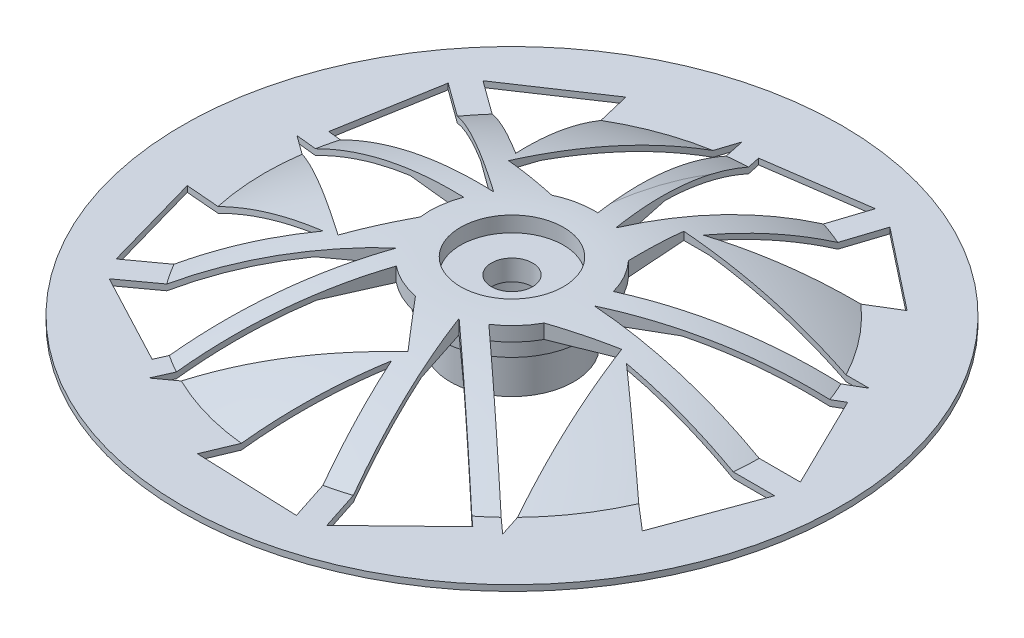
SolidWorks part; units mm, degrees
ref_plane "Front Plane" through (0, 0, 0) normal (0, 0, 1) x (1, 0, 0)
ref_plane "Top Plane" through (0, 0, 0) normal (0, 1, 0) x (1, 0, 0)
ref_plane "Right Plane" through (0, 0, 0) normal (1, 0, 0) x (0, 0, -1)
sketch "Sketch1" plane through (0, 0, 0) normal (0, 0, 1) x (1, 0, 0)
  line L0 (0, 0) -> (19.05, 0) construction
  line L1 (19.05, 0) -> (19.05, 12.7) construction
  line L2 (19.05, 12.7) -> (22.225, 12.7) construction
  line L3 (22.225, 12.7) -> (22.225, 19.05) construction
  line L4 (22.225, 19.05) -> (76.2, 19.05) construction
  line L5 (76.2, 19.05) -> (76.2, 6.35) construction
  line L6 (0, 0) -> (0, 22.225) construction
  line L7 (15.875, 0) -> (15.875, 22.225) construction
  line L8 (15.875, 22.225) -> (84.6295, 22.225) construction
  line L9 (15.875, 23.8125) -> (15.875, 19.05)
  line L10 (15.875, 0) -> (19.05, 0)
  line L11 (19.05, 0) -> (19.05, 12.7)
  line L12 (19.05, 12.7) -> (22.225, 12.7)
  line L13 (22.225, 12.7) -> (22.225, 19.05)
  line L14 (22.225, 19.05) -> (43.5904, 19.05)
  line L16 (76.2, 8.17) -> (101.6, 8.17) construction
  line L17 (101.6, 8.17) -> (101.6, 6.35) construction
  line L18 (101.6, 6.35) -> (76.2, 6.35) construction
  line L19 (76.2, 8.17) -> (101.6, 8.17)
  line L20 (101.6, 8.17) -> (101.6, 6.35)
  line L21 (101.6, 6.35) -> (76.2, 6.35)
  line L22 (6.35, 19.05) -> (15.875, 19.05)
  line L24 (0, 12.7) -> (0, 19.05) construction
  line L26 (6.35, 12.7) -> (6.35, 19.05) construction
  line L27 (6.35, 12.7) -> (15.875, 12.7)
  line L28 (6.35, 19.05) -> (6.35, 12.7)
  line L29 (15.875, 12.7) -> (15.875, 0)
  arc A0 (43.5904, 19.05) -> (76.2, 6.35) centre (15.875, -100.33) cw
  arc A1 (15.875, 23.8125) -> (76.2, 8.17) centre (15.875, -100.33) cw
  arc A3 (15.875, 22.225) -> (76.2, 6.35) centre (15.875, -100.33) cw construction
  arc A4 (15.875, 23.8125) -> (76.9814, 7.7319) centre (15.875, -100.33) cw construction
  dimension "D1" = 19.05
  dimension "D2" = 12.7
  dimension "D3" = 6.35
  dimension "D4" = 3.175
  dimension "D5" = 53.975
  dimension "D6" = 12.7
  dimension "D7" = 22.225
  dimension "D8" = 15.875
  dimension "D9" = 22.225
  dimension "D11" = 25.4
  dimension "D12" = 101.6
  dimension "D13" = 6.35
  dimension "D14" = 6.35
  dimension "D10" = 1.5875
revolve "Revolve1" add sketch "Sketch1" angle 360 about L6
sketch "Sketch3" plane through (0, 6.35, 0) normal (0, -1, 0) x (-1, 0, 0)
  line L0 (-25.4, 0) -> (-88.9, 0) construction
  line L1 (-88.9, 0) -> (-74.8934, 28.575) construction
  line L2 (-74.8934, 28.575) -> (-25.4, 0) construction
  line L3 (-50.1467, 14.2875) -> (-46.9717, 19.7868) construction
  line L4 (-19.4754, 3.9118) -> (-74.468, 35.6618) construction
  line L5 (-19.4754, 3.9118) -> (-17.318, 35.6618) construction
  line L6 (-17.318, 35.6618) -> (-74.468, 35.6618) construction
  line L7 (-74.468, 35.6618) -> (-17.318, 35.6618)
  line L8 (-17.318, 35.6618) -> (-18.5631, 17.337)
  line L9 (-74.468, 35.6618) -> (-24.4735, 6.7975)
  line L10 (-74.8934, 28.575) -> (-25.4, 0)
  line L11 (-25.4, 0) -> (-88.9, 0)
  line L12 (-88.9, 0) -> (-74.8934, 28.575)
  line L13 (-57.15, 0) -> (-57.15, -7.6239) construction
  line L14 (-42.9185, -7.6239) -> (-88.5725, -7.6239) construction
  line L15 (-42.9185, -7.6239) -> (-77.5983, -37.417) construction
  line L16 (-77.5983, -37.417) -> (-88.5725, -7.6239) construction
  line L17 (-88.5725, -7.6239) -> (-42.9185, -7.6239)
  line L18 (-42.9185, -7.6239) -> (-77.5983, -37.417)
  line L19 (-77.5983, -37.417) -> (-88.5725, -7.6239)
  line L20 (10.9045, 81.8434) -> (-1.098, 25.3763)
  line L21 (10.9045, 81.8434) -> (28.5648, 27.4905)
  line L22 (28.5648, 27.4905) -> (10.7521, 23.012)
  line L23 (-27.4716, 84.5489) -> (4.0331, 80.058)
  line L24 (4.0331, 80.058) -> (-7.849, 24.1568)
  line L25 (-7.849, 24.1568) -> (-27.4716, 84.5489)
  line L26 (-59.5649, 62.2379) -> (-34.6211, 81.8815)
  line L27 (-34.6211, 81.8815) -> (-20.5133, 38.462)
  line L28 (-20.5133, 38.462) -> (-59.5649, 62.2379)
  line L29 (81.2073, 14.9202) -> (23.795, 8.8859)
  line L30 (81.2073, 14.9202) -> (34.972, -18.6717)
  line L31 (34.972, -18.6717) -> (25.2083, -3.1147)
  line L32 (71.9216, 52.2541) -> (77.386, 20.9035)
  line L33 (77.386, 20.9035) -> (20.549, 14.9297)
  line L34 (20.549, 14.9297) -> (71.9216, 52.2541)
  line L35 (40.7852, 75.8821) -> (67.1755, 58.2294)
  line L36 (67.1755, 58.2294) -> (30.2406, 31.3947)
  line L37 (30.2406, 31.3947) -> (40.7852, 75.8821)
  line L38 (39.2844, -72.6222) -> (15.8041, -19.8845)
  line L39 (39.2844, -72.6222) -> (-6.9509, -39.0302)
  line L40 (-6.9509, -39.0302) -> (4.8275, -24.937)
  line L41 (71.9216, -52.2541) -> (43.794, -67.1389)
  line L42 (43.794, -67.1389) -> (20.549, -14.9297)
  line L43 (20.549, -14.9297) -> (71.9216, -52.2541)
  line L44 (84.7715, -15.3402) -> (76.1379, -45.8938)
  line L45 (76.1379, -45.8938) -> (39.203, -19.059)
  line L46 (39.203, -19.059) -> (84.7715, -15.3402)
  line L47 (-56.9282, -59.8032) -> (-14.0275, -21.1752)
  line L48 (-56.9282, -59.8032) -> (-39.2679, -5.4503)
  line L49 (-39.2679, -5.4503) -> (-22.2247, -12.2972)
  line L50 (-27.4716, -84.5489) -> (-50.3198, -62.3976)
  line L51 (-50.3198, -62.3976) -> (-7.849, -24.1568)
  line L52 (-7.849, -24.1568) -> (-27.4716, -84.5489)
  line L53 (11.6065, -85.3629) -> (-20.1197, -86.5934)
  line L54 (-20.1197, -86.5934) -> (-6.0118, -43.1738)
  line L55 (-6.0118, -43.1738) -> (11.6065, -85.3629)
  circle A0 centre (0, 0) radius 22.225 construction
  circle A1 centre (0, 0) radius 101.6 construction
  circle A2 centre (0, 0) radius 88.9 construction
  circle A3 centre (0, 0) radius 25.4
  circle A4 centre (0, 0) radius 43.5904 construction
  point P14 (-46.9717, 19.7868)
  point P67 (0, 0)
  circle M19 centre (0, 0) radius 76.2
  dimension "D1" = 203.2
  dimension "D2" = 177.8
  dimension "D3" = 50.8
  dimension "D4" = 44.45
  dimension "D5" = 57.15
  dimension "D6" = 30
  dimension "D7" = 63.5
  dimension "D8" = 57.15
  dimension "D9" = 30
  dimension "D10" = 6.35
  dimension "D11" = 45.72
  dimension "D12" = 31.75
  dimension "D13" = 5
extrude "Cut-Extrude1" cut sketch "Sketch3" against normal through all contours L28 L27 M19 | L28 L27 L26 M19 | L25 L24 M19 | L25 L24 L23 M19 | L37 L36 M19 | L37 L36 L35 M19 | A3 L22 L21 L20 M19 | L21 L20 M19 | L34 L33 L32 M19 | L34 L33 M19 | A3 L31 L30 L29 M19 | L30 L29 M19 | L46 L45 M19 | L46 L45 L44 M19 | L43 L42 L41 M19 | L43 L42 M19 | A3 L40 L39 L38 M19 | L39 L38 M19 | L55 L54 L53 M19 | L55 L54 M19 | L52 L51 M19 | L52 L51 L50 M19 | A3 L49 L48 L47 M19 | L48 L47 M19 | L18 L17 M19 | L19 L18 L17 M19 | L12 L11 L10 M19 | L11 L10 M19 | A3 L8 L7 L9 M19 | L7 L9 M19 region at (70.2574, 6.35, -34.5996) region at (37.4156, 6.35, -25.6822) region at (34.2368, 6.35, -55.3494) region at (43.7412, 6.35, -68.4563) region at (79.1773, 6.35, -11.2708) region at (58.1907, 6.35, -8.9969) region at (9.4253, 6.35, -58.1228) region at (13.748, 6.35, -78.785) region at (35.9873, 6.35, 27.6481) region at (78.6225, 6.35, 20.4462) region at (63.2202, 6.35, 15.4572) region at (-12.8632, 6.35, -43.5206) region at (-11.1954, 6.35, -77.5106) region at (54.6169, 6.35, 56.1269) region at (26.5385, 6.35, 52.5624) region at (-52.3655, 6.35, -26.925) region at (35.1863, 6.35, 71.8193) region at (-15.1742, 6.35, 42.7697) region at (-42.0607, 6.35, -49.665) region at (-51.589, 6.35, -62.7545) region at (-70.6806, 6.35, -37.421) region at (-45.3655, 6.35, -1.215) region at (4.8503, 6.35, 81.0927) region at (4.8355, 6.35, 64.9025) region at (-77.1766, 6.35, -13.3046) region at (-36.5023, 6.35, 69.2879) region at (-41.789, 6.35, 41.4823) region at (-57.431, 6.35, 55.6575) region at (-75.6249, 6.35, 29.6719) region at (-60.2317, 6.35, 24.6548)
